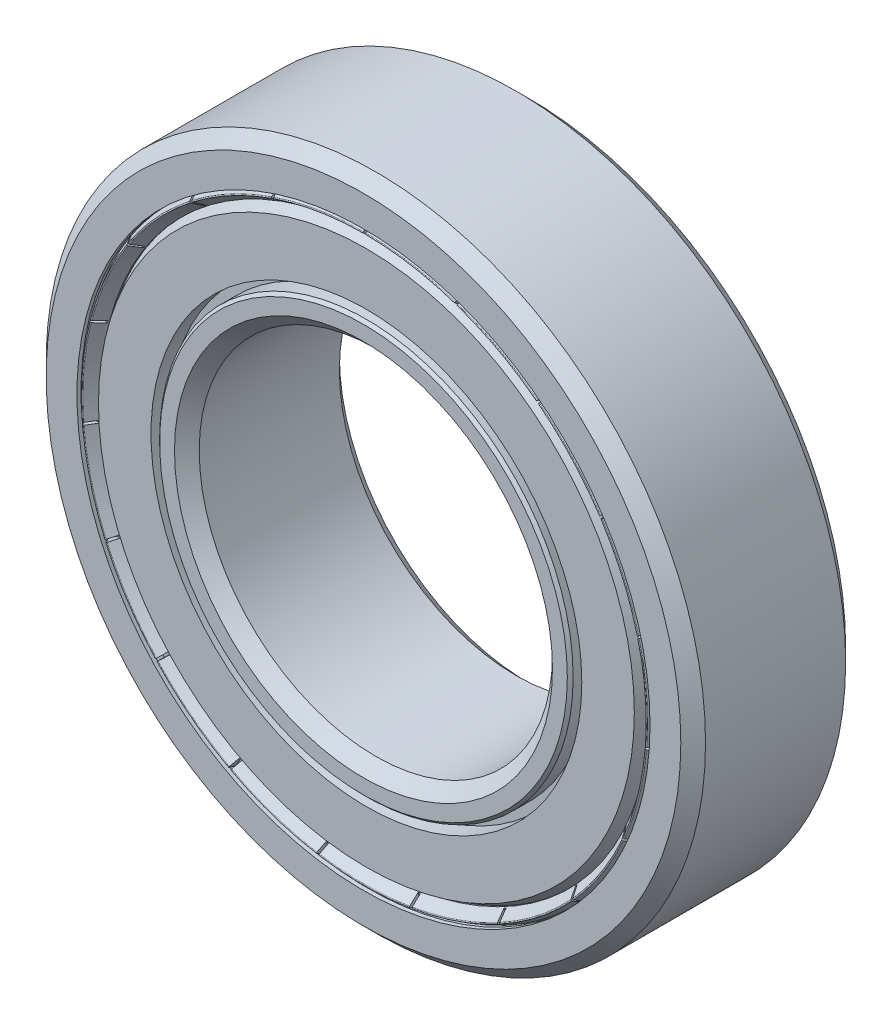
SolidWorks part; units mm, degrees
ref_plane "Front Plane" through (0, 0, 0) normal (0, 0, 1) x (1, 0, 0)
ref_plane "Top Plane" through (0, 0, 0) normal (0, 1, 0) x (1, 0, 0)
ref_plane "Right Plane" through (0, 0, 0) normal (1, 0, 0) x (0, 0, -1)
sketch "Sketch1" plane through (0, 0, 0) normal (0, 0, 1) x (1, 0, 0)
  circle A0 centre (0, 0) radius 7.5
  circle A1 centre (0, 0) radius 14
  dimension "OD" = 28
  dimension "ID" = 15
sketch "Sketch2" plane through (0, 0, 0) normal (1, 0, 0) x (0, 0, -1)
  line L0 (-3.5, 14) -> (3.5, 14)
  line L1 (-3.5, 7.5) -> (-3.5, -7.5) construction
  line L2 (3.5, 14) -> (3.5, -14) construction
  line L3 (-3.5, 0) -> (3.5, 0) construction
  line L6 (0, 14) -> (0, 7.5) construction
  circle A0 centre (0, 10.75) radius 2.275 construction
  point P8 (0, 14)
  dimension "Approx. Ball Dia." = 4.55
  dimension "Width" = 7
  dimension "For Shaft Diameter" = 15
  dimension "For Housing ID" = 28
sketch "Sketch3" plane through (0, 0, 0) normal (1, 0, 0) x (0, 0, -1)
  line L0 (0, 0) -> (0, 15) construction
  line L1 (-3.5, 7.5) -> (-3.5, -7.5) construction
  line L2 (2.975, 14) -> (-2.975, 14)
  line L3 (-2.975, 14) -> (-3.5, 13.475)
  line L4 (-3.5, 13.475) -> (-3.5, 12.1679)
  line L5 (-3.5, 12.1679) -> (-3.325, 12.1679)
  line L6 (-3.325, 12.1679) -> (-3.325, 12.5965)
  line L7 (-3.325, 12.5965) -> (-3.2013, 12.7202)
  line L8 (-3.2013, 12.7202) -> (-1.1375, 12.7202)
  line L10 (-3.5, 14) -> (3.5, 14) construction
  line L12 (-3.325, 12.5965) -> (-3.325, 13.025) construction
  line L13 (3.2013, 12.7202) -> (1.1375, 12.7202)
  line L14 (3.325, 12.5965) -> (3.2013, 12.7202)
  line L15 (3.325, 12.1679) -> (3.325, 12.5965)
  line L16 (3.5, 12.1679) -> (3.325, 12.1679)
  line L17 (3.5, 13.475) -> (3.5, 12.1679)
  line L18 (2.975, 14) -> (3.5, 13.475)
  line L19 (2.975, 7.5) -> (-2.975, 7.5)
  line L20 (-2.975, 7.5) -> (-3.5, 8.025)
  line L21 (-3.5, 8.025) -> (-3.5, 8.656)
  line L22 (-3.5, 8.656) -> (-3.3763, 8.7798)
  line L23 (-3.3763, 8.7798) -> (-1.1375, 8.7798)
  line L25 (3.3763, 8.7798) -> (1.1375, 8.7798)
  line L26 (3.5, 8.656) -> (3.3763, 8.7798)
  line L27 (3.5, 8.025) -> (3.5, 8.656)
  line L28 (2.975, 7.5) -> (3.5, 8.025)
  circle A2 centre (0, 10.75) radius 2.275 construction
  arc A3 (-1.1375, 12.7202) -> (1.1375, 12.7202) centre (0, 10.75) cw
  arc A4 (-1.1375, 8.7798) -> (1.1375, 8.7798) centre (0, 10.75) ccw
  point P5 (0, 13.025)
  point P31 (0, 14)
  point P37 (0, 7.5)
  dimension "D1" = 45
  dimension "D2" = 0.175
  dimension "D3" = 2.275
  dimension "D4" = 0.525
revolve "Revolve1" add sketch "Sketch3" angle 360 about L3
sketch "Sketch4" plane through (0, 0, 0) normal (1, 0, 0) x (0, 0, -1)
  line L0 (0, 13.025) -> (0, 8.475)
  line L1 (0, 14) -> (0, 7.5) construction
  circle A0 centre (0, 10.75) radius 2.275 construction
  arc A1 (0, 8.475) -> (0, 13.025) centre (0, 10.75) cw
revolve "Revolve2" add sketch "Sketch4" angle 360 about L6
pattern_circular "CirPattern1" count 10 over 360 about axis through (0, 0, 3.5) along (0, 0, -1) of bodies 106
sketch "Sketch5" plane through (0, 0, 0) normal (1, 0, 0) x (0, 0, -1)
  line L0 (-2.275, 10.75) -> (-2.275, 8.7798) construction
  line L1 (-3.3763, 8.7798) -> (-1.1375, 8.7798) construction
  line L3 (-2.275, 8.7798) -> (-2.6421, 8.7798)
  line L4 (-2.6421, 8.7798) -> (-2.6421, 9.1469)
  line L5 (-2.6421, 9.1469) -> (-3.3763, 9.1469)
  line L6 (-3.3763, 9.1469) -> (-3.3763, 11.377)
  line L7 (-3.3763, 11.377) -> (-2.6421, 11.8008)
  line L8 (-2.6421, 11.8008) -> (-2.275, 11.8008)
  line L9 (-2.275, 11.8008) -> (-2.275, 8.7798)
  line L10 (0, 10.75) -> (0, 14) construction
  line L11 (2.6421, 11.8008) -> (2.275, 11.8008)
  line L12 (3.3763, 11.377) -> (2.6421, 11.8008)
  line L13 (3.3763, 9.1469) -> (3.3763, 11.377)
  line L14 (2.6421, 9.1469) -> (3.3763, 9.1469)
  line L15 (2.6421, 8.7798) -> (2.6421, 9.1469)
  line L16 (2.275, 8.7798) -> (2.6421, 8.7798)
  line L17 (2.275, 11.8008) -> (2.275, 8.7798)
  line L18 (-3.3763, 11.377) -> (-3.0092, 11.377) construction
  line L19 (-3.0092, 11.377) -> (-2.6421, 11.377) construction
  line L20 (-2.6421, 11.377) -> (-2.275, 11.377) construction
  line L21 (-2.6421, 11.8008) -> (-2.6421, 12.1679) construction
  circle A0 centre (0, 10.75) radius 2.275 construction
  dimension "D1" = 30
revolve "Revolve3" add sketch "Sketch5" angle 360 about L3
sketch "Sketch6" plane through (0, 0, 0) normal (1, 0, 0) x (0, 0, -1)
  line L0 (-2.8961, 12.1679) -> (-3.1937, 12.1679)
  line L1 (-3.1937, 12.1679) -> (-3.5, 11.9911)
  line L2 (-3.5, 11.9911) -> (-3.0011, 11.6418)
  line L4 (-3.3763, 11.377) -> (-2.6421, 11.8008) construction
  line L5 (-2.8961, 11.6542) -> (-2.8961, 12.1679)
  line L6 (-3.5, 12.1679) -> (-3.325, 12.1679) construction
  line L7 (-3.0011, 11.6418) -> (-2.9661, 11.6418)
  line L8 (-2.9661, 11.6418) -> (-2.8961, 11.6542)
  line L9 (-3.5, 13.475) -> (-3.5, -13.475) construction
  line L11 (-2.9661, 11.6418) -> (-2.9311, 11.6418) construction
  line L12 (-2.9311, 11.6418) -> (-2.8961, 11.6418) construction
  point P27 (-3.0449, 12.1679)
  dimension "D1" = 30
  dimension "D3" = 10
  dimension "D2" = 35
  dimension "D4" = 0.035
  dimension "D5" = 0.3062
revolve "Revolve4" add sketch "Sketch6" angle 360 about L3
fillet "Fillet1" radius 0.035 1 edges at (11.9911, 0, 3.5)
sketch "Sketch7" plane through (0, 0, 0) normal (0, 0, 1) x (1, 0, 0)
  line L0 (-0.05, 12.1679) -> (-0.05, 12.2679)
  line L1 (-0.05, 12.1679) -> (0.05, 12.1679) construction
  line L2 (-0.05, 12.1679) -> (-0.05, 11.6418)
  line L3 (-0.05, 11.6418) -> (0.05, 11.6418) construction
  line L4 (0.05, 12.1679) -> (0.05, 11.6418)
  line L5 (-0.05, 12.2679) -> (0.05, 12.2679)
  line L6 (0.05, 12.2679) -> (0.05, 12.1679)
  line L7 (-0.05, 11.6418) -> (-0.05, 11.5418)
  line L8 (-0.05, 11.5418) -> (0.05, 11.5418)
  line L9 (0.05, 11.5418) -> (0.05, 11.6418)
  dimension "D1" = 0.1
extrude "Cut-Extrude1" cut sketch "Sketch7" along normal through all from vertex starting at point (0, 12.1679, 3.0449)
pattern_circular "CirPattern2" count 19 over 360 about axis through (0, 0, 3.5) along (0, 0, -1) of "Cut-Extrude1"
mirror "Mirror1" about plane through (0, 0, 0) normal (0, 0, 1) of bodies 120
equation "\"Approx. Ball Dia.@Sketch2\"=( \"OD@Sketch1\" - \"ID@Sketch1\" )  * .5 * .7"
equation "\"D2@Sketch3\"=\"Width@Sketch2\"*.025"
equation "\"D3@Sketch3\"=\"Approx. Ball Dia.@Sketch2\"*.5"
equation "\"D4@Sketch3\"=\"Width@Sketch2\"*.075"
equation "\"Approx No of Balls\"= ( pi * \"OD@Sketch1\" ) * .5 / \"Approx. Ball Dia.@Sketch2\""
equation "\"D1@CirPattern1\"=\"Approx No of Balls\""
equation "\"D4@Sketch6\"=\"D2@Sketch3\"*.2"
equation "\"D1@CirPattern2\"=\"Approx No of Balls\"*2"
equation "\"D5@Sketch6\"=\"D2@Sketch3\"*1.75"
equation "\"D1@Fillet1\"=\"d4@sketch6\""
